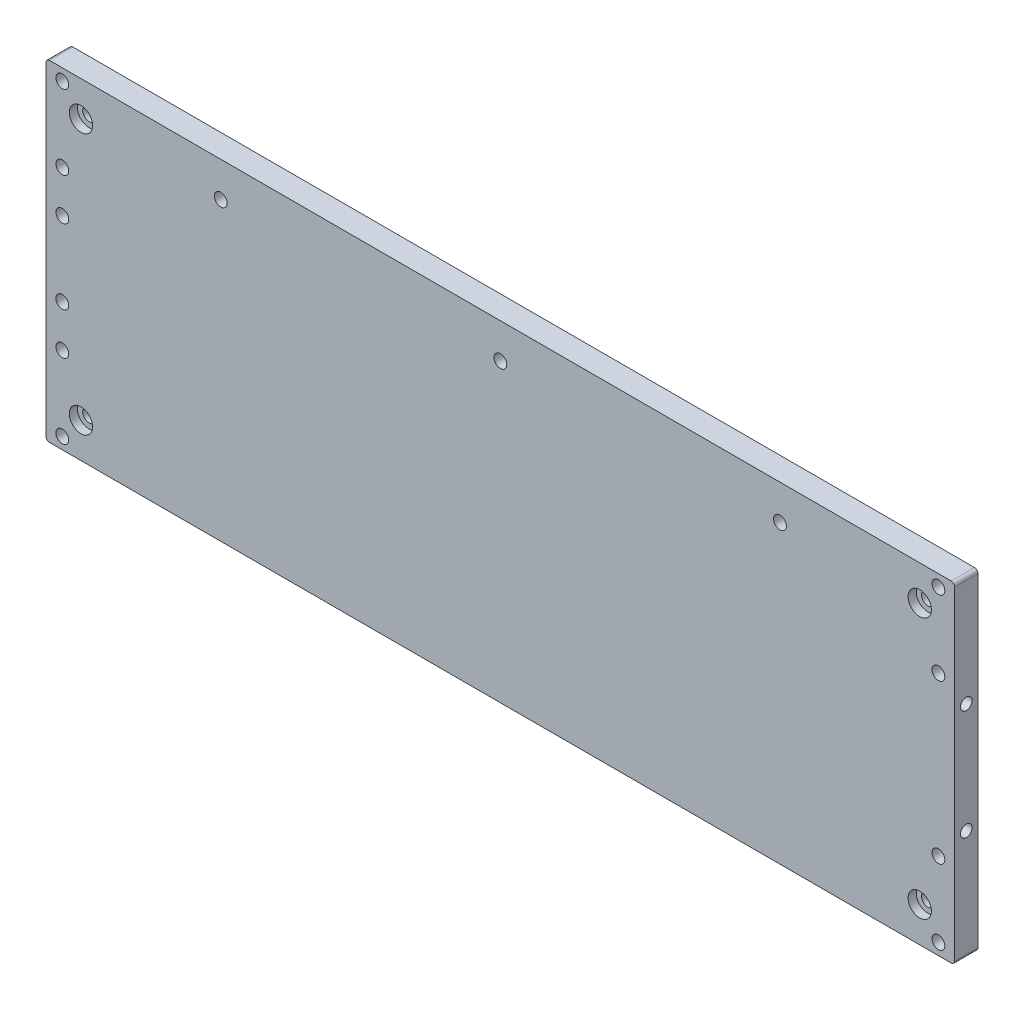
SolidWorks part; units mm, degrees
ref_plane "Front Plane" through (0, 0, 0) normal (0, 0, 1) x (1, 0, 0)
ref_plane "Top Plane" through (0, 0, 0) normal (0, 1, 0) x (1, 0, 0)
ref_plane "Right Plane" through (0, 0, 0) normal (1, 0, 0) x (0, 0, -1)
sketch "Sketch1" plane through (0, 0, 0) normal (0, 0, 1) x (1, 0, 0)
  line L1 (195, -71) -> (-195, -71)
  line L2 (195, -71) -> (195, 71)
  line L3 (195, 71) -> (-195, 71)
  line L4 (-195, -71) -> (-195, 71)
  line L5 (195, -71) -> (-195, 71) construction
  line L6 (195, 71) -> (-195, -71) construction
  point P0 (0, 0)
  dimension "D1" = 390
  dimension "D2" = 142
extrude "Boss-Extrude1" add sketch "Sketch1" along normal mid plane 10
sketch "Sketch2" plane through (0, 0, -5) normal (0, 0, -1) x (-1, 0, 0)
  line L0 (-188, 71) -> (-188, -71) construction
  line L1 (-195, 71) -> (195, 71) construction
  line L2 (195, -71) -> (-195, -71) construction
  line L3 (-195, -71) -> (-195, 71) construction
  line L4 (188, 71) -> (188, -71) construction
  line L5 (195, 71) -> (195, -71) construction
  line L6 (-195, 66) -> (195, 66) construction
  line L7 (-195, -66) -> (195, -66) construction
  line L8 (-195, 34) -> (195, 34) construction
  line L9 (-195, -34) -> (195, -34) construction
  circle A0 centre (-188, 66) radius 2.75
  circle A1 centre (-188, -66) radius 2.75
  circle A2 centre (188, 66) radius 2.75
  circle A3 centre (188, -66) radius 2.75
  circle A4 centre (-188, 34) radius 2.75
  circle A5 centre (-188, -34) radius 2.75
  circle A6 centre (188, 34) radius 2.75
  circle A7 centre (188, -34) radius 2.75
  dimension "D5" = 5.5
  dimension "D6" = 5.5
  dimension "D7" = 5.5
  dimension "D8" = 5.5
  dimension "D11" = 5.5
  dimension "D12" = 5.5
  dimension "D13" = 5.5
  dimension "D14" = 5.5
  dimension "D1" = 7
  dimension "D2" = 7
  dimension "D3" = 5
  dimension "D4" = 5
  dimension "D9" = 32
  dimension "D10" = 32
extrude "Cut-Extrude1" cut sketch "Sketch2" against normal through all
sketch "Sketch3" plane through (0, 0, 5) normal (0, 0, 1) x (1, 0, 0)
  line L0 (-195, 56) -> (195, 56) construction
  line L1 (-195, 71) -> (-195, -71) construction
  line L2 (195, -71) -> (195, 71) construction
  line L3 (-195, -56) -> (195, -56) construction
  line L4 (-180, 71) -> (-180, -71) construction
  line L5 (195, 71) -> (-195, 71) construction
  line L6 (-195, -71) -> (195, -71) construction
  line L7 (180, 71) -> (180, -71) construction
  line L8 (-120, 71) -> (-120, -71) construction
  line L9 (120, 71) -> (120, -71) construction
  circle A0 centre (-180, 56) radius 2.75
  circle A1 centre (180, 56) radius 2.75
  circle A2 centre (180, -56) radius 2.75
  circle A3 centre (-180, -56) radius 2.75
  circle A4 centre (0, 56) radius 2.75
  circle A5 centre (-120, 56) radius 2.75
  circle A6 centre (120, 56) radius 2.75
  dimension "D5" = 5.5
  dimension "D6" = 5.5
  dimension "D7" = 5.5
  dimension "D8" = 5.5
  dimension "D9" = 5.5
  dimension "D12" = 5.5
  dimension "D13" = 5.5
  dimension "D1" = 15
  dimension "D2" = 15
  dimension "D3" = 15
  dimension "D4" = 15
  dimension "D10" = 75
  dimension "D11" = 75
extrude "Cut-Extrude2" cut sketch "Sketch3" against normal through all
sketch "Sketch4" plane through (0, 0, 5) normal (0, 0, 1) x (1, 0, 0)
  circle A0 centre (-180, 56) radius 5
  circle A1 centre (-180, -56) radius 5
  circle A2 centre (180, 56) radius 5
  circle A3 centre (180, -56) radius 5
  dimension "D1" = 10
  dimension "D2" = 10
  dimension "D3" = 10
  dimension "D4" = 10
extrude "Cut-Extrude3" cut sketch "Sketch4" against normal blind 3.5
sketch "Sketch5" plane through (195, 0, 0) normal (1, 0, 0) x (0, 0, -1)
  line L0 (0, 71) -> (0, -71) construction
  line L1 (-5, 71) -> (5, 71) construction
  line L2 (-5, -71) -> (5, -71) construction
  circle A0 centre (0, 23.6) radius 2.5
  circle A1 centre (0, -23.6) radius 2.5
  dimension "D1" = 5
  dimension "D2" = 5
  dimension "D3" = 23.6
  dimension "D4" = 23.6
extrude "Cut-Extrude4" cut sketch "Sketch5" against normal blind 10
sketch "Sketch6" plane through (0, 0, 5) normal (0, 0, 1) x (1, 0, 0)
  line L0 (-188, 34) -> (-188, -34) construction
  line L1 (-188, 0) -> (195, 0) construction
  line L2 (195, -71) -> (195, 71) construction
  circle A0 centre (-188, 16) radius 2.75
  circle A1 centre (-188, -16) radius 2.75
  circle A2 centre (-188, 34) radius 2.75 construction
  dimension "D1" = 16
  dimension "D3" = 5.5
  dimension "D4" = 5.5
  dimension "D2" = 16
extrude "Cut-Extrude5" cut sketch "Sketch6" against normal through all
fillet "Fillet1" radius 1.5 4 edges at (-195, -71, 0) (195, -71, 0) (195, 71, 0) (-195, 71, 0)
equation "\"D3@Sketch5\"=47.2/2"
equation "\"D4@Sketch5\"=47.2/2"
equation "\"D1@Sketch6\"=32/2"
equation "\"D2@Sketch6\"=32/2"
